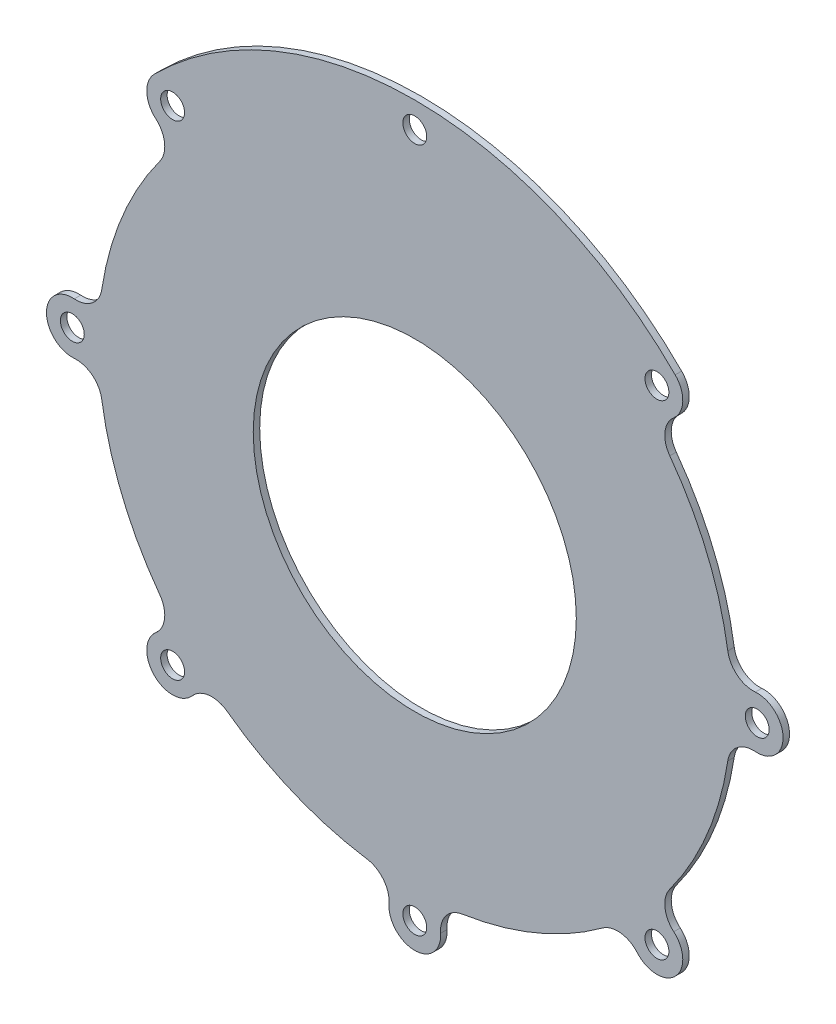
SolidWorks part; units mm, degrees
ref_plane "Ön Düzlem" through (0, 0, 0) normal (0, 0, 1) x (1, 0, 0)
ref_plane "Üst Düzlem" through (0, 0, 0) normal (0, 1, 0) x (1, 0, 0)
ref_plane "Sağ Düzlem" through (0, 0, 0) normal (1, 0, 0) x (0, 0, -1)
sketch "NPTH" plane through (0, 0, 0) normal (0, 0, 1) x (1, 0, 0)
  circle A0 centre (0, 0) radius 25
  arc A1 (-39.4685, 29.0385) -> (-48.4418, 7.3751) centre (0, 0) ccw
  arc A2 (40.3051, 40.3051) -> (-40.3051, 40.3051) centre (0, 0) ccw
  circle A3 centre (0, -53) radius 1.85
  circle A4 centre (0, 0) radius 53 construction
  arc A5 (-3.9886, -52.6981) -> (3.9886, -52.6981) centre (0, -53) ccw
  arc A6 (7.3751, -48.4418) -> (4.0028, -52.8486) centre (7.9772, -52.3962) ccw
  arc A7 (-4.0028, -52.8486) -> (-7.3751, -48.4418) centre (-7.9772, -52.3962) ccw
  arc A8 (-29.0385, -39.4685) -> (-34.5392, -40.2001) centre (-31.409, -42.6904) ccw
  circle A9 centre (-37.4767, -37.4767) radius 1.85
  arc A10 (-40.0836, -34.4428) -> (-34.4428, -40.0836) centre (-37.4767, -37.4767) ccw
  arc A11 (-40.2001, -34.5392) -> (-39.4685, -29.0385) centre (-42.6904, -31.409) ccw
  arc A12 (-48.4418, -7.3751) -> (-52.8486, -4.0028) centre (-52.3962, -7.9772) ccw
  circle A13 centre (-53, 0) radius 1.85
  arc A14 (-52.6981, 3.9886) -> (-52.6981, -3.9886) centre (-53, 0) ccw
  arc A15 (-52.8486, 4.0028) -> (-48.4418, 7.3751) centre (-52.3962, 7.9772) ccw
  arc A16 (-39.4685, 29.0385) -> (-40.2001, 34.5392) centre (-42.6904, 31.409) ccw
  circle A17 centre (-37.4767, 37.4767) radius 1.85
  arc A18 (-40.3051, 40.3051) -> (-40.0836, 34.4428) centre (-37.4767, 37.4767) ccw
  circle A21 centre (0, 53) radius 1.85
  circle A25 centre (37.4767, 37.4767) radius 1.85
  arc A26 (40.0836, 34.4428) -> (40.3051, 40.3051) centre (37.4767, 37.4767) ccw
  arc A27 (40.2001, 34.5392) -> (39.4685, 29.0385) centre (42.6904, 31.409) ccw
  arc A28 (48.4418, 7.3751) -> (52.8486, 4.0028) centre (52.3962, 7.9772) ccw
  circle A29 centre (53, 0) radius 1.85
  arc A30 (52.6981, -3.9886) -> (52.6981, 3.9886) centre (53, 0) ccw
  arc A31 (52.8486, -4.0028) -> (48.4418, -7.3751) centre (52.3962, -7.9772) ccw
  arc A32 (39.4685, -29.0385) -> (40.2001, -34.5392) centre (42.6904, -31.409) ccw
  circle A33 centre (37.4767, -37.4767) radius 1.85
  arc A34 (34.4428, -40.0836) -> (40.0836, -34.4428) centre (37.4767, -37.4767) ccw
  arc A35 (34.5392, -40.2001) -> (29.0385, -39.4685) centre (31.409, -42.6904) ccw
  arc A36 (7.3751, -48.4418) -> (29.0385, -39.4685) centre (0, 0) ccw
  arc A37 (39.4685, -29.0385) -> (48.4418, -7.3751) centre (0, 0) ccw
  arc A38 (33.7795, 45.9124) -> (28.0999, 44.9377) centre (31.409, 42.6904) ccw [skipped]
  circle A39 centre (0, 53) radius 4 [skipped]
  circle A40 centre (7.9772, 52.3962) radius 4 [skipped]
  circle A41 centre (-7.9772, 52.3962) radius 4 [skipped]
  circle A42 centre (-31.409, 42.6904) radius 4 [skipped]
  arc A43 (-29.0385, -39.4685) -> (-7.3751, -48.4418) centre (0, 0) ccw
  arc A44 (48.4418, 7.3751) -> (39.4685, 29.0385) centre (0, 0) ccw
  arc A45 (-48.4418, -7.3751) -> (-39.4685, -29.0385) centre (0, 0) ccw
  point P72 (0, 0)
  dimension "D1" = 50
  dimension "D2" = 98
  dimension "D3" = 114
  dimension "D4" = 3.7
  dimension "D5" = 106
  dimension "D6" = 8
  dimension "D7" = 8
extrude "Boss-Extrude1" add sketch "NPTH" along normal blind 1 contours A12 A45 A11 A10 A8 A43 A7 A5 A6 A36 A35 A34 A32 A37 A31 A30 A28 A44 A27 A26 A2 A18 A16 A1 A15 A14 A0 A3 A9 A13 A17 A21 A25 A29 A33 region at (-31.409, 42.6904, 0) region at (-37.1188, 32.0431, 0) region at (-4.2309, 55.8991, 0) region at (-7.9772, 52.3962, 0) region at (4.2309, 55.8991, 0) region at (2.7484, 55.7484, 0) region at (7.9772, 52.3962, 0)
